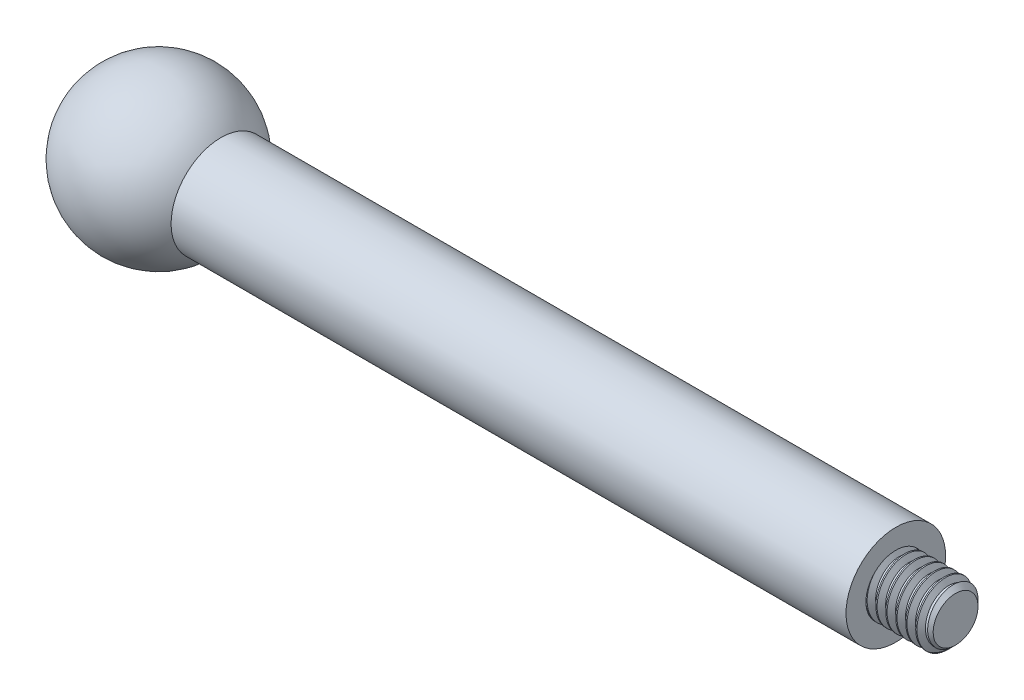
SolidWorks part; units mm, degrees
ref_plane "Front Plane" through (0, 0, 0) normal (0, 0, 1) x (1, 0, 0)
ref_plane "Top Plane" through (0, 0, 0) normal (0, 1, 0) x (1, 0, 0)
ref_plane "Right Plane" through (0, 0, 0) normal (1, 0, 0) x (0, 0, -1)
sketch "Sketch1" plane through (0, 0, 0) normal (0, 0, 1) x (1, 0, 0)
  line L0 (0, 0) -> (-88, 0)
  line L2 (0, 0) -> (0, 3)
  line L5 (0, 3) -> (-6, 3)
  line L6 (-6, 3) -> (-6, 5)
  line L7 (-6, 5) -> (-73.755, 5)
  arc A0 (-73.755, 5) -> (-88, 0) centre (-80, 0) ccw
  point P1 (-83.6402, 0)
  point P9 (-48.1371, 0)
  dimension "D2" = 8
  dimension "D1" = 5
  dimension "D3" = 74
  dimension "D4" = 6
  dimension "D5" = 3
revolve "Revolve1" add sketch "Sketch1" angle 360 about L0
chamfer "Chamfer1" distance 0.75 angle 45 1 edges at (0, 3, 0)
thread "Thread1" pitch 1 method cut profile "Thread Profile1" start angle 0, offset 1, length 0, pitch 1, diameter 6
ref_plane "Plane1" through (1, 0, 3) normal (0, -1, 0) x (0, 0, 1)
sketch "Thread Profile1" plane through (1, 0, 3) normal (0, -1, 0) x (0, 0, 1)
  line L0 (0, 0) -> (0, 1) construction
  line L11 (0, 0) -> (0, 0.875)
  line L12 (0, 0.875) -> (-0.5413, 0.5625)
  line L13 (-0.5413, 0.5625) -> (-0.5413, 0.3125)
  line L15 (-0.5413, 0.3125) -> (0, 0)
  line L17 (-0.5413, 0.4375) -> (0, 0.4375) construction
  point P2 (0, 0)
  dimension "Pitch" = 1
  dimension "Profile_Angle" = 60
  dimension "Profile_Land" = 0.25
  dimension "Profile_Height" = 0.5413
